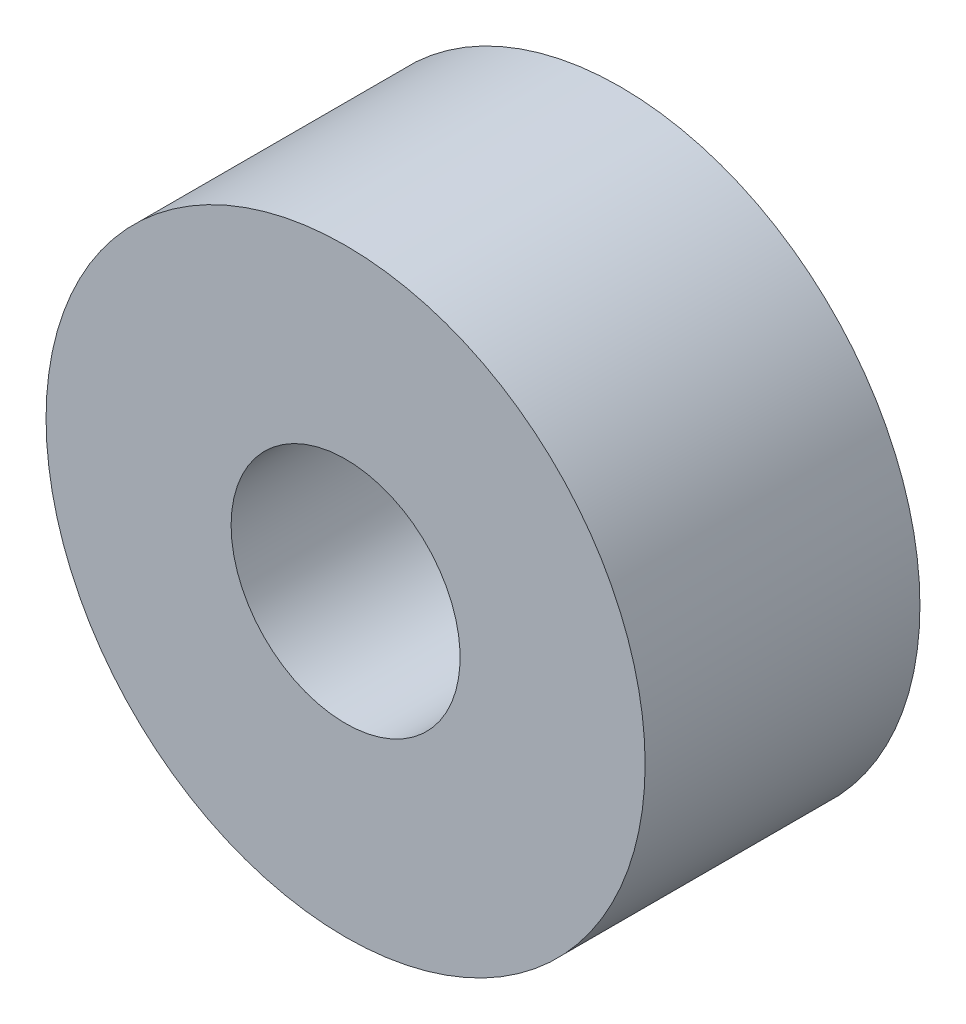
SolidWorks part; units mm, degrees
ref_plane "Front Plane" through (0, 0, 0) normal (0, 0, 1) x (1, 0, 0)
ref_plane "Top Plane" through (0, 0, 0) normal (0, 1, 0) x (1, 0, 0)
ref_plane "Right Plane" through (0, 0, 0) normal (1, 0, 0) x (0, 0, -1)
sketch "Sketch1" plane through (0, 0, 0) normal (0, 0, 1) x (1, 0, 0)
  circle A0 centre (0, 0) radius 10.3822
  circle A1 centre (0, 0) radius 3.9688
  dimension "D1" = 20.7645
  dimension "D2" = 7.9375
extrude "Boss-Extrude1" add sketch "Sketch1" along normal blind 9.525
